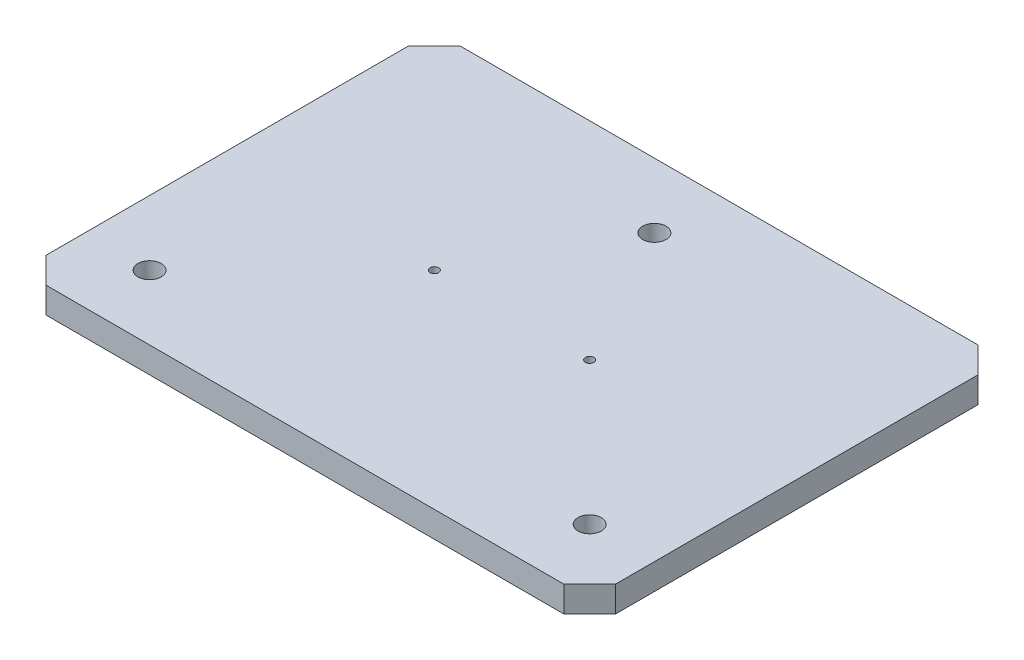
SolidWorks part; units mm, degrees
ref_plane "Front Plane" through (0, 0, 0) normal (0, 0, 1) x (1, 0, 0)
ref_plane "Top Plane" through (0, 0, 0) normal (0, 1, 0) x (1, 0, 0)
ref_plane "Right Plane" through (0, 0, 0) normal (1, 0, 0) x (0, 0, -1)
sketch "Sketch1" plane through (0, 0, 0) normal (0, 1, 0) x (1, 0, 0)
  line L1 (110, -80) -> (-110, -80)
  line L2 (110, -80) -> (110, 80)
  line L3 (110, 80) -> (-110, 80)
  line L4 (-110, -80) -> (-110, 80)
  line L5 (110, -80) -> (-110, 80) construction
  line L6 (110, 80) -> (-110, -80) construction
  point P0 (0, 0)
  dimension "D1" = 220
  dimension "D2" = 160
extrude "Boss-Extrude1" add sketch "Sketch1" along normal blind 10
chamfer "Chamfer1" distance 10 angle 45 4 edges at (-110, 5, -80) (110, 5, -80) (110, 5, 80) (-110, 5, 80)
sketch "Sketch2" plane through (0, 10, 0) normal (0, 1, 0) x (1, 0, 0)
  point P0 (-85, -55)
  point P1 (85, -55)
  point P2 (0, 55)
  dimension "D1" = 55
  dimension "D2" = 85
  dimension "D3" = 55
  dimension "D4" = 85
hole_wizard "M10x1.0 Tapped Hole1" positions "3DSketch1" profile "Sketch3" tap size "M10x1.0" standard "BSI" end condition through all
sketch3d "3DSketch1"
  point P0 (0, 10, -55)
  point P3 (-85, 10, 55)
  point P6 (85, 10, 55)
sketch "Sketch3" plane through (0, 10, -55) normal (1, 0, 0) x (0, 0, 1)
  line L0 (0, 0) -> (0, 10)
  line L1 (0, 10) -> (4.5, 10)
  line L2 (4.5, 10) -> (4.5, 0)
  line L5 (4.5, 0) -> (0, 0)
  line L11 (0, -6.35) -> (0, 107.95) construction
  dimension "Thru Tap Drill Dia." = 9
  dimension "Thru Tap Drill Depth" = 10
cosmetic thread "Hole Thread1"
cosmetic thread "Hole Thread2"
cosmetic thread "Hole Thread3"
sketch "Sketch4" plane through (0, 10, 0) normal (0, 1, 0) x (1, 0, 0)
  line L0 (0, 0) -> (30, 0) construction
  point P4 (30, 0)
  dimension "D1" = 30
hole_wizard "M4x0.7 Tapped Hole1" positions "3DSketch2" profile "Sketch5" tap size "M4x0.7" standard "BSI" end condition through all
sketch3d "3DSketch2"
  point P0 (30, 10, 0)
sketch "Sketch5" plane through (30, 10, 0) normal (1, 0, 0) x (0, 0, 1)
  line L0 (0, 0) -> (0, 10)
  line L1 (0, 10) -> (1.65, 10)
  line L2 (1.65, 10) -> (1.65, 0)
  line L5 (1.65, 0) -> (0, 0)
  line L11 (0, -6.35) -> (0, 107.95) construction
  dimension "Thru Tap Drill Dia." = 3.3
  dimension "Thru Tap Drill Depth" = 10
cosmetic thread "Hole Thread4"
mirror "Mirror1" about plane through (0, 0, 0) normal (1, 0, 0) of "M4x0.7 Tapped Hole1"
cosmetic thread "Hole Thread5"
equation "\"D4@Sketch2\"=\"D2@Sketch2\""
